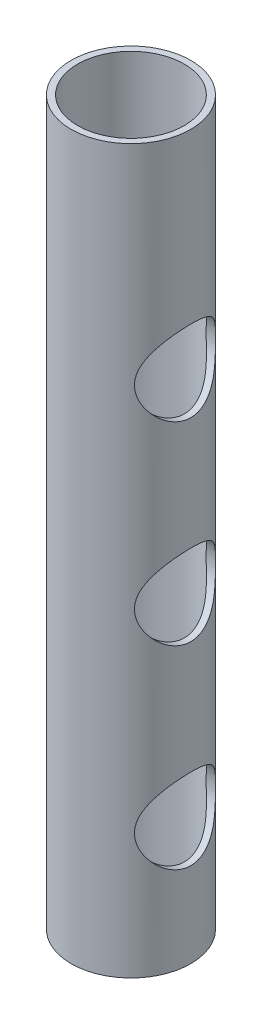
SolidWorks part; units mm, degrees
material "PTFE (general)"
ref_plane "Front Plane" through (0, 0, 0) normal (0, 0, 1) x (1, 0, 0)
ref_plane "Top Plane" through (0, 0, 0) normal (0, 1, 0) x (1, 0, 0)
ref_plane "Right Plane" through (0, 0, 0) normal (1, 0, 0) x (0, 0, -1)
sketch "Sketch1" plane through (0, 0, 0) normal (0, 1, 0) x (1, 0, 0)
  circle A0 centre (0, 0) radius 18.5
  circle A1 centre (0, 0) radius 16.5
  dimension "D1" = 2
  dimension "D2" = 33
extrude "Boss-Extrude1" add sketch "Sketch1" along normal blind 223.5
sketch "Sketch2" plane through (0, 0, 0) normal (1, 0, 0) x (0, 0, -1)
  line L0 (16.5, 223.5) -> (-16.5, 223.5) construction
  circle A0 centre (0, 158.8) radius 12.53
  circle A1 centre (0, 98.8) radius 12.53
  circle A2 centre (0, 38.8) radius 12.53
  dimension "D2" = 25.06
  dimension "D3" = 25.06
  dimension "D4" = 25.06
  dimension "D1" = 64.7
  dimension "D5" = 60
  dimension "D6" = 60
extrude "Cut-Extrude1" cut sketch "Sketch2" along normal through all
